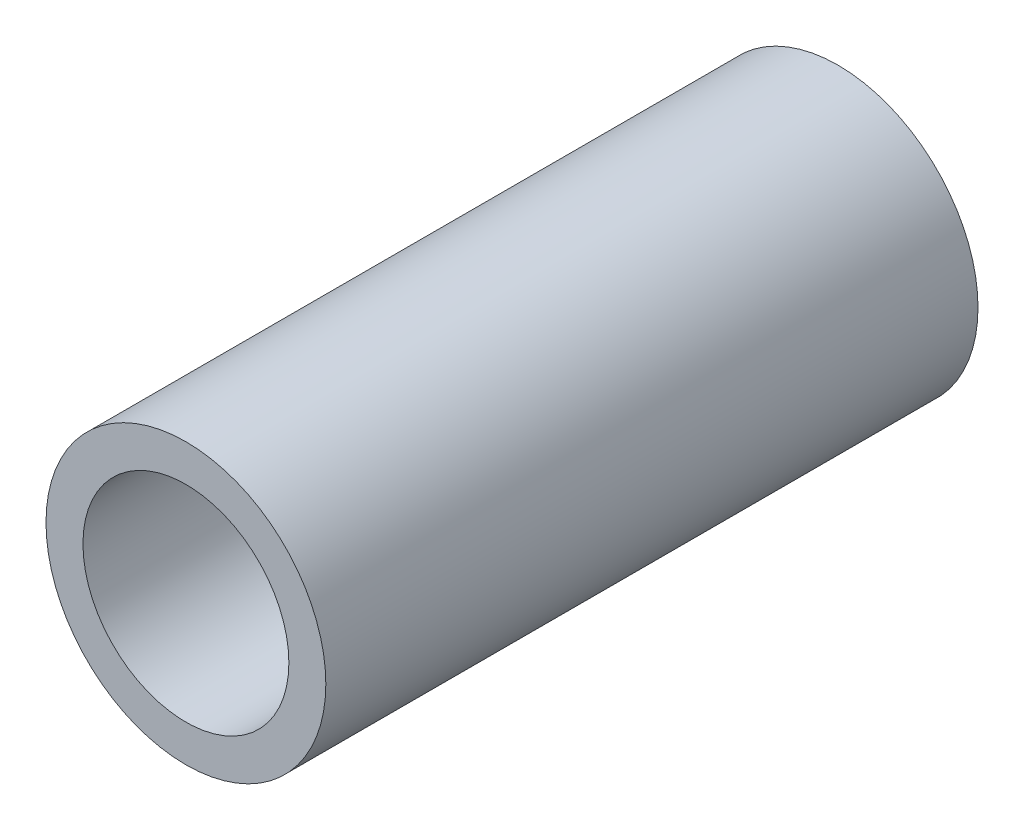
SolidWorks part; units mm, degrees
ref_plane "Front Plane" through (0, 0, 0) normal (0, 0, 1) x (1, 0, 0)
ref_plane "Top Plane" through (0, 0, 0) normal (0, 1, 0) x (1, 0, 0)
ref_plane "Right Plane" through (0, 0, 0) normal (1, 0, 0) x (0, 0, -1)
sketch "Sketch1" plane through (0, 0, 0) normal (0, 0, 1) x (1, 0, 0)
  circle A0 centre (0, 0) radius 4.0894
  circle A1 centre (0, 0) radius 5.5562
  dimension "D1" = 11.1125
  dimension "D2" = 8.1788
extrude "Boss-Extrude1" add sketch "Sketch1" along normal up to surface (25.9 mm away)
